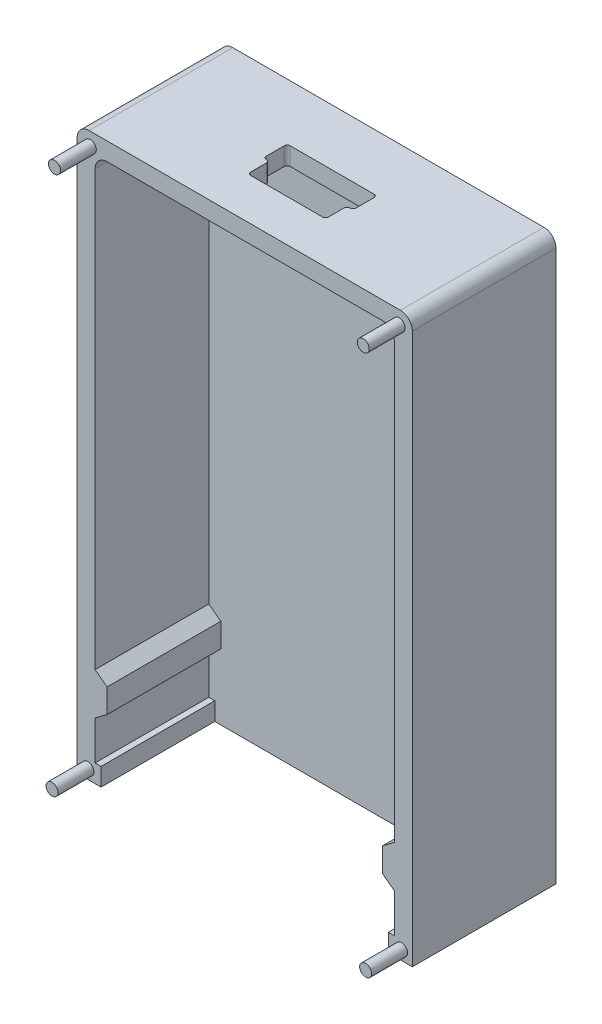
SolidWorks part; units mm, degrees
ref_plane "Ebene vorne" through (0, 0, 0) normal (0, 0, 1) x (1, 0, 0)
ref_plane "Ebene oben" through (0, 0, 0) normal (0, 1, 0) x (1, 0, 0)
ref_plane "Ebene rechts" through (0, 0, 0) normal (1, 0, 0) x (0, 0, -1)
sketch "Skizze1" plane through (0, 0, 0) normal (0, 0, 1) x (1, 0, 0)
  line L0 (0, 0) -> (0, 47)
  line L1 (0, 47) -> (28, 47)
  line L2 (28, 47) -> (28, 0)
  line L3 (28, 0) -> (0, 0)
  dimension "D1" = 47
  dimension "D2" = 28
extrude "Aufsatz-Linear austragen1" add sketch "Skizze1" along normal blind 12
sketch "Skizze2" plane through (0, 0, 12) normal (0, 0, 1) x (1, 0, 0)
  line L0 (0, 47) -> (0, 0) construction
  line L1 (2.5, 45.5) -> (25.5, 45.5)
  line L2 (1.5, 44.5) -> (1.5, 8.2519)
  line L3 (1.5, 1.5) -> (2, 1.5)
  line L4 (26.5, 44.5) -> (26.5, 8.2519)
  line L5 (28, 47) -> (0, 47) construction
  line L6 (28, 0) -> (28, 47) construction
  line L7 (0, 0) -> (28, 0) construction
  line L8 (26, 1.5) -> (26.5, 1.5)
  line L10 (2, 1.5) -> (2, 0)
  line L12 (26, 1.5) -> (26, 0)
  line L13 (2, 0) -> (26, 0)
  line L14 (26.5, 8.2519) -> (25.5, 7.5)
  line L15 (25.5, 7.5) -> (25.5, 5.5)
  line L16 (25.5, 5.5) -> (26.5, 4.7519)
  line L17 (26.5, 4.7519) -> (26.5, 1.5)
  line L18 (14, 0) -> (14, 53.6399) construction
  line L19 (2.5, 5.5) -> (1.5, 4.7519)
  line L20 (2.5, 7.5) -> (2.5, 5.5)
  line L21 (1.5, 8.2519) -> (2.5, 7.5)
  line L22 (1.5, 4.7519) -> (1.5, 1.5)
  line L23 (-12.8344, 23.5) -> (47.2834, 23.5) construction
  arc A0 (25.5, 45.5) -> (26.5, 44.5) centre (25.5, 44.5) cw
  arc A1 (2.5, 45.5) -> (1.5, 44.5) centre (2.5, 44.5) ccw
  point P22 (25.5, 6.5)
  dimension "D6" = 1
  dimension "D1" = 1.5
  dimension "D2" = 1.5
  dimension "D3" = 1.5
  dimension "D4" = 1.5
  dimension "D5" = 24
  dimension "D7" = 2
  dimension "D8" = 1
  dimension "D9" = 3.5
  dimension "D10" = 126.8
  dimension "D11" = 6.5
  dimension "D15" = 23.5
extrude "Schnitt-Linear austragen1" cut sketch "Skizze2" against normal blind 9.5
fillet "Verrundung2" radius 1 2 edges at (0, 47, 6) (28, 47, 6)
sketch "Skizze3" plane through (0, 0, 12) normal (0, 0, 1) x (1, 0, 0)
  line L1 (26, 0) -> (28, 0) construction
  line L2 (28, 0) -> (28, 46) construction
  line L4 (0, 46) -> (0, 0) construction
  line L6 (27, 47) -> (1, 47) construction
  line L7 (0, 0) -> (2, 0) construction
  circle A0 centre (1.1, 45.9) radius 0.5
  circle A1 centre (26.9, 45.9) radius 0.5
  circle A2 centre (0.9, 0.8) radius 0.5
  circle A3 centre (27.1, 0.8) radius 0.5
  dimension "D1" = 1
  dimension "D2" = 1
  dimension "D3" = 1
  dimension "D4" = 1
  dimension "D11" = 1.1
  dimension "D5" = 0.8
  dimension "D6" = 0.9
  dimension "D7" = 0.8
  dimension "D8" = 0.9
  dimension "D9" = 1.1
  dimension "D10" = 1.1
  dimension "D12" = 1.1
extrude "Aufsatz-Linear austragen2" add sketch "Skizze3" along normal blind 3
sketch "Skizze4" plane through (0, 47, 0) normal (0, 1, 0) x (1, 0, 0)
  line L1 (10.25, -4.7) -> (17.75, -4.7)
  line L2 (10.25, -4.7) -> (10.25, -6.7)
  line L3 (10.75, -8.5) -> (17.25, -8.5)
  line L4 (17.75, -4.7) -> (17.75, -6.7)
  line L6 (10.75, -6.7) -> (10.75, -8.5)
  line L7 (10.75, -8.5) -> (17.25, -8.5)
  line L8 (17.25, -6.7) -> (17.25, -8.5)
  line L10 (17.25, -6.7) -> (17.75, -6.7)
  line L11 (27, -12) -> (1, -12) construction
  line L12 (28, 0) -> (28, -12) construction
  line L13 (10.25, -6.7) -> (10.75, -6.7)
  dimension "D1" = 7.5
  dimension "D2" = 3.8
  dimension "D3" = 6.5
  dimension "D4" = 0.5
  dimension "D5" = 2
  dimension "D6" = 3.5
  dimension "D7" = 10.25
extrude "Schnitt-Linear austragen4" cut sketch "Skizze4" against normal blind 10 contours L2 L13 L6 L3 L8 L10 L4 L1 region at (14, 47, 6.5326)
fillet "Verrundung3" radius 0.25 8 edges at (17.25, 46.25, 6.7) (17.25, 46.25, 8.5) (10.75, 46.25, 6.7) (10.25, 46.25, 6.7) (17.75, 46.25, 6.7) (17.75, 46.25, 4.7) (10.25, 46.25, 4.7) (10.75, 46.25, 8.5)
